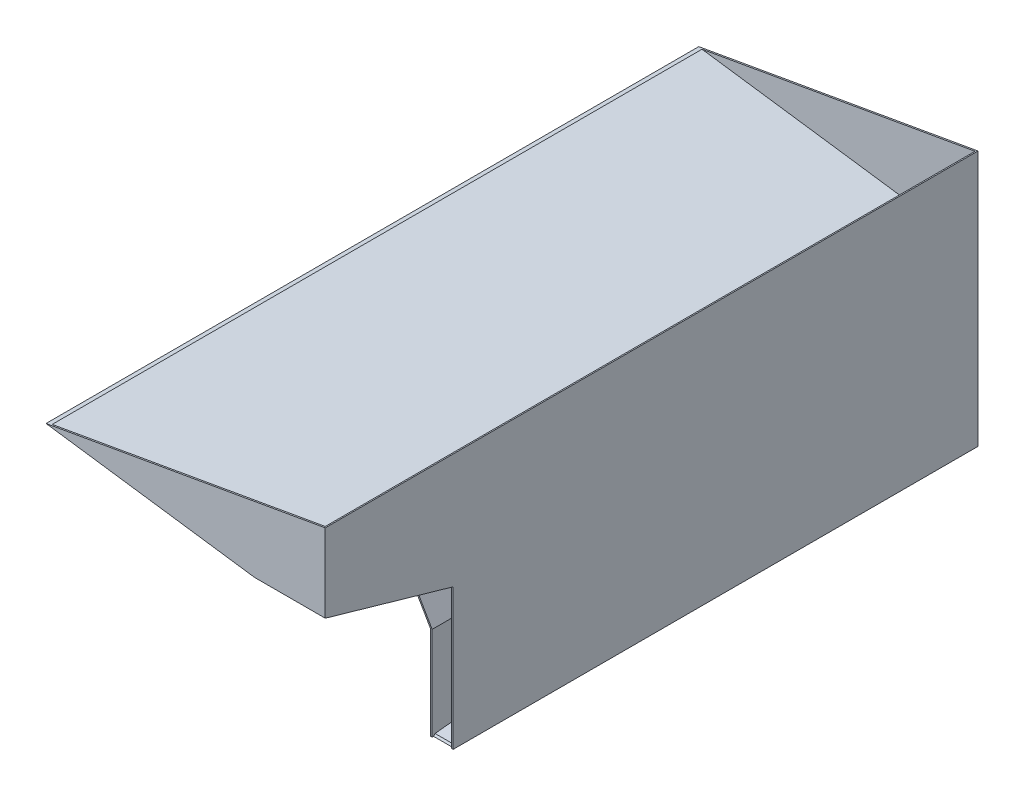
SolidWorks part; units mm, degrees
ref_plane "Front Plane" through (0, 0, 0) normal (0, 0, 1) x (1, 0, 0)
ref_plane "Top Plane" through (0, 0, 0) normal (0, 1, 0) x (1, 0, 0)
ref_plane "Right Plane" through (0, 0, 0) normal (1, 0, 0) x (0, 0, -1)
other "Center of Mass"
sketch "Sketch2" plane through (0, 0, 0) normal (0, 0, 1) x (1, 0, 0)
  line L0 (0, 0) -> (-105, 181.8653)
  line L1 (-105, 181.8653) -> (-551.9888, 244.1441)
  line L2 (-551.9888, 244.1441) -> (48.35, 350)
  line L3 (48.35, 350) -> (48.35, -200)
  line L4 (48.35, -200) -> (0, -200)
  line L5 (0, -200) -> (0, 0)
  dimension "D1" = 150
  dimension "D2" = 609.6
  dimension "D3" = 550
  dimension "D4" = 200
  dimension "D5" = 48.35
  dimension "D6" = 210
  dimension "D7" = 280
extrude "Boss-Extrude1" add sketch "Sketch2" along normal mid plane 1403.35
shell "Shell1" thickness 3.175 removed face at (-251.8194, 297.072, 0)
sketch "Sketch3" plane through (0, 0, 701.675) normal (0, 0, 1) x (1, 0, 0)
  line L1 (3.175, -187.3) -> (45.175, -187.3)
  line L2 (3.175, -187.3) -> (3.175, 102.7)
  line L3 (3.175, 102.7) -> (45.175, 102.7)
  line L4 (45.175, -187.3) -> (45.175, 102.7)
  line L6 (0, -200) -> (48.35, -200) construction
  point P6 (24.175, -200)
  point P7 (24.175, -187.3)
  dimension "D1" = 42
  dimension "D2" = 12.7
  dimension "D3" = 290
extrude "Cut-Extrude1" cut sketch "Sketch3" against normal blind 20
scale "Scale1" [suppressed]
sketch "Sketch6" plane through (0, 0, 701.675) normal (0, 0, 1) x (1, 0, 0)
  line L1 (-167.2364, 157.2102) -> (-3.283, 157.2102)
  line L2 (-167.2364, 157.2102) -> (-167.2364, -5.4179)
  line L3 (-167.2364, -5.4179) -> (-3.283, -5.4179)
  line L4 (-3.283, 157.2102) -> (-3.283, -5.4179)
extrude "Cut-Extrude3" [suppressed] cut sketch "Sketch6" against normal blind 200
sketch "Sketch7" plane through (0, 0, 0) normal (-1, 0, 0) x (0, 0, 1)
  line L1 (701.675, -200) -> (426.675, -200)
  line L2 (701.675, -200) -> (701.675, 102.7)
  line L3 (701.675, 102.7) -> (426.675, 102.7)
  line L4 (426.675, -200) -> (426.675, 102.7)
  dimension "D1" = 275
  dimension "D2" = 302.7
extrude "Cut-Extrude5" cut sketch "Sketch7" against normal mid plane 200
sketch "Sketch9" plane through (48.35, 0, 0) normal (1, 0, 0) x (0, 0, -1)
  line L0 (-701.675, 102.7) -> (-701.675, 350) construction
  line L1 (-426.675, 102.7) -> (-701.675, 102.7)
  line L2 (-426.675, 102.7) -> (-426.675, 181.7)
  line L3 (-426.675, 181.7) -> (-701.675, 181.7)
  line L4 (-701.675, 102.7) -> (-701.675, 181.7)
  line L5 (-701.675, 181.7) -> (-426.675, 102.7)
  line M2 (-701.675, 102.7) -> (-426.675, 102.7)
  line M7 (-701.675, 350) -> (-701.675, 102.7)
  dimension "D1" = 79
extrude "Cut-Extrude7" cut sketch "Sketch9" against normal through all contours L5 M7 M2 region at (48.35, 129.0333, 610.0083)
sketch "Sketch11" plane through (0, -18.3572, 5.2735) normal (0, -0.9611, 0.2761) x (1, 0, 0)
  line L0 (48.35, 724.5674) -> (48.35, 438.445)
  line L1 (48.35, 438.445) -> (-59.2939, 438.445)
  line L2 (-59.2939, 438.445) -> (-104.9045, 724.5674)
  line L3 (-104.9045, 724.5674) -> (48.35, 724.5674)
extrude "Boss-Extrude3" add sketch "Sketch11" against normal blind 6.35
sketch "Sketch12" plane through (3.175, 0, 0) normal (1, 0, 0) x (0, 0, -1)
  line L0 (-426.675, -196.825) -> (688.975, -79.5655)
  line L1 (688.975, -79.5655) -> (688.975, -82.7405)
  line L2 (-396.4669, -196.825) -> (-426.675, -196.825)
  line L3 (701.675, -200) -> (701.675, 350) construction
  line L4 (688.975, -82.7405) -> (-396.4669, -196.825)
  line L5 (-396.4669, -196.825) -> (-396.4669, -193.65)
  line M5 (-426.675, -196.825) -> (698.5, -196.825)
  dimension "D1" = 3.175
  dimension "D2" = 12.7
  dimension "D3" = 6
  dimension "D4" = 3.175
  dimension "D5" = 3.175
extrude "Boss-Extrude4" add sketch "Sketch12" along normal up to surface (42 mm away) contours L5 L4 L1 L0 | L5 L0 M5 region at (3.175, -195.7667, 406.5363) region at (3.175, -138.1952, -146.2541) up to face at (45.175, 100.5897, 182.6102)
chamfer "Chamfer1" distance 6.35 angle 45 1 edges at (24.175, -196.825, 426.675) first distance on face at (24.175, -138.1952, -131.15)
